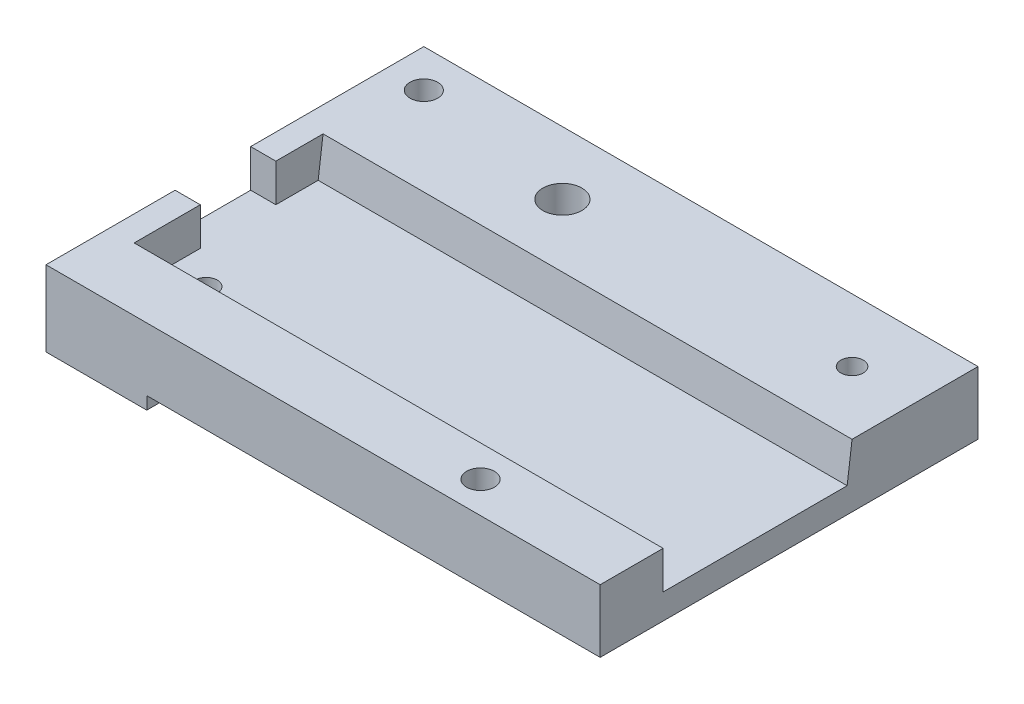
SolidWorks part; units mm, degrees
material "CA"
ref_plane "Front Plane" through (0, 0, 0) normal (0, 0, 1) x (1, 0, 0)
ref_plane "Top Plane" through (0, 0, 0) normal (0, 1, 0) x (1, 0, 0)
ref_plane "Right Plane" through (0, 0, 0) normal (1, 0, 0) x (0, 0, -1)
sketch "Sketch1" plane through (0, 0, 0) normal (0, 1, 0) x (1, 0, 0)
  line L1 (-22, 15) -> (22, 15)
  line L2 (-22, 15) -> (-22, -15)
  line L3 (-22, -15) -> (22, -15)
  line L4 (22, 15) -> (22, -15)
  line L5 (-22, 15) -> (22, -15) construction
  line L6 (-22, -15) -> (22, 15) construction
  point P0 (0, 0)
  dimension "D1" = 44
  dimension "D2" = 30
extrude "Boss-Extrude1" add sketch "Sketch1" along normal blind 5
sketch "Sketch2" plane through (0, 0, 0) normal (0, -1, 0) x (1, 0, 0)
  line L0 (-22, 15) -> (22, 15) construction
  line L1 (-22, -15) -> (-14, -15)
  line L2 (-22, -15) -> (-22, 15)
  line L3 (-22, 15) -> (-14, 15)
  line L4 (-14, -15) -> (-14, 15)
  dimension "D1" = 8
extrude "Boss-Extrude2" add sketch "Sketch2" along normal blind 1
sketch "Sketch3" plane through (0, 5, 0) normal (0, 1, 0) x (1, 0, 0)
  line L0 (22, 15) -> (-22, 15) construction
  line L1 (-22, 15) -> (-22, -15) construction
  circle A0 centre (-6, 10) radius 1.55
  dimension "D3" = 3.1
  dimension "D1" = 5
  dimension "D2" = 16
extrude "Cut-Extrude1" cut sketch "Sketch3" against normal through all
sketch "Sketch4" plane through (0, 5, 0) normal (0, 1, 0) x (1, 0, 0)
  line L1 (22, -10) -> (-20, -10)
  line L2 (-20, -10) -> (-20, -4.75)
  line L3 (-20, 5) -> (22, 5)
  line L5 (-22, 15) -> (-22, -15) construction
  line L6 (-20, 1.25) -> (-22, 1.25)
  line L7 (-20, -4.75) -> (-22, -4.75)
  line L8 (-22, 1.25) -> (-22, -4.75)
  line L9 (-20, 1.25) -> (-20, 5)
  line L11 (22, -15) -> (22, 15) construction
  line L12 (22, 5) -> (22, -10)
  dimension "D4" = 2
  dimension "D5" = 6
  dimension "D6" = 5.25
extrude "Cut-Extrude2" cut sketch "Sketch4" against normal blind 3
sketch "Sketch5" plane through (0, 2, 0) normal (0, 1, 0) x (1, 0, 0)
  line L1 (-20, -4.75) -> (-20, -10) construction
  line L2 (-20, -10) -> (22, -10) construction
  circle A0 centre (-17.14, -7.14) radius 0.889
  point P6 (-19.7373, -7.0883)
  dimension "D3" = 1.778
  dimension "D1" = 2.86
  dimension "D2" = 2.86
sketch "Sketch6" plane through (0, 5, 0) normal (0, 1, 0) x (1, 0, 0)
  line L0 (22, 15) -> (-22, 15) construction
  line L1 (22, 5) -> (22, 15) construction
  circle A0 centre (17, 10) radius 0.889
  point P2 (0, 0)
  point P5 (22, 10)
  dimension "D1" = 1.778
  dimension "D2" = 5
  dimension "D3" = 5
sketch "Sketch7" plane through (0, 5, 0) normal (0, 1, 0) x (1, 0, 0)
  line L0 (22, 15) -> (-22, 15) construction
  line L1 (-22, 15) -> (-22, 1.25) construction
  line L2 (-22, -15) -> (22, -15) construction
  line L3 (22, -15) -> (22, -10) construction
  circle A0 centre (-19, 12) radius 1.1
  circle A1 centre (10, -12.5) radius 1.1
  dimension "D1" = 2.2
  dimension "D6" = 2.2
  dimension "D2" = 3
  dimension "D3" = 3
  dimension "D4" = 2.5
  dimension "D5" = 12
extrude "Cut-Extrude4" cut sketch "Sketch7" against normal blind 2
extrude "Cut-Extrude5" cut sketch "Sketch5" against normal through all contours A0
extrude "Cut-Extrude6" cut sketch "Sketch6" against normal through all contours A0
chamfer "Chamfer2" distance 3 distance2 0.39 1 edges at (1, 2, -5) first distance on face at (1, 3.5, -5)
